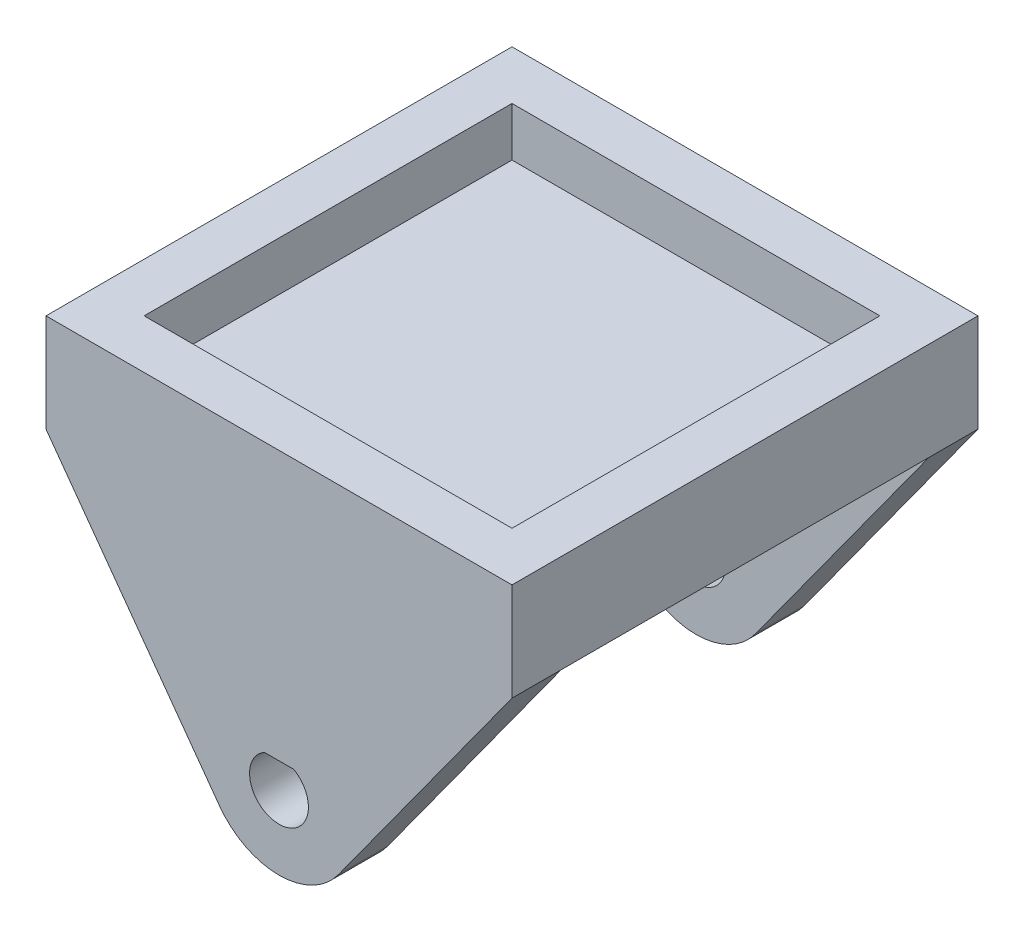
SolidWorks part; units mm, degrees
ref_plane "Front Plane" through (0, 0, 0) normal (0, 0, 1) x (1, 0, 0)
ref_plane "Top Plane" through (0, 0, 0) normal (0, 1, 0) x (1, 0, 0)
ref_plane "Right Plane" through (0, 0, 0) normal (1, 0, 0) x (0, 0, -1)
sketch "Sketch1" plane through (0, 0, 0) normal (0, 0, 1) x (1, 0, 0)
  line L0 (-3, 5.1962) -> (3, 5.1962)
  line L1 (-47.5, 40) -> (47.5, 40)
  line L2 (-12.1474, -8.8) -> (-47.5, 40)
  line L3 (12.1474, -8.8) -> (47.5, 40)
  line L4 (-47.5, 40) -> (-47.5, 60)
  line L5 (-47.5, 60) -> (47.5, 60)
  line L6 (47.5, 60) -> (47.5, 40)
  circle A0 centre (0, 0) radius 15
  circle A1 centre (0, 0) radius 6
  dimension "D1" = 30
  dimension "D2" = 12
  dimension "D3" = 6
  dimension "D4" = 40
  dimension "D5" = 95
  dimension "D7" = 20
extrude "Boss-Extrude1" add sketch "Sketch1" against normal blind 10 contours A0 L3 L1 L2 | A0 A1 | L0 A1 region at (0, 5.5196, 0) region at (0, 25.2208, 0) region at (-4.4946, 13.8655, 0)
extrude "Boss-Extrude2" add sketch "Sketch1<3>" against normal blind 95 contours L6 L5 L4 L1 region at (0, 50, 0)
sketch "Sketch1<3>" plane through (0, 0, 0) normal (0, 0, 1) x (1, 0, 0) same geometry as "Sketch1"
sketch "Sketch6" plane through (0, 40, 0) normal (0, -1, 0) x (-1, 0, 0)
  line L0 (47.5, 47.5) -> (-47.5, 47.5) construction
  line L1 (47.5, 95) -> (47.5, 10) construction
  line L2 (-47.5, 95) -> (-47.5, 10) construction
  line L3 (47.5, 95) -> (-47.5, 95) construction
  line L4 (-47.5, 47.5) -> (47.5, 47.5) construction
  dimension "D1" = 47.5
sketch "Sketch7" plane through (0, 60, 0) normal (0, 1, 0) x (1, 0, 0)
  line L0 (-47.5, 47.5) -> (47.5, 47.5) construction
  line L1 (-47.5, 95) -> (-47.5, 0) construction
ref_plane "Plane2" through (0, 0, -47.5) normal (0, 0, 1) x (1, 0, 0)
mirror "Mirror2" about plane through (0, 0, -47.5) normal (0, 0, 1) of "Boss-Extrude1"
sketch "Sketch8" plane through (0, 60, 0) normal (0, 1, 0) x (1, 0, 0)
  line L0 (-47.5, 0) -> (47.5, 0) construction
  line L1 (-37.5, 85) -> (37.5, 85)
  line L2 (-37.5, 85) -> (-37.5, 10)
  line L3 (-37.5, 10) -> (37.5, 10)
  line L4 (37.5, 85) -> (37.5, 10)
  line L5 (47.5, 95) -> (47.5, 0) construction
  line L7 (-47.5, 95) -> (-47.5, 0) construction
  line L8 (-47.5, 95) -> (47.5, 95) construction
  dimension "D1" = 10
  dimension "D2" = 10
  dimension "D3" = 10
  dimension "D4" = 10
extrude "Cut-Extrude2" cut sketch "Sketch8" against normal blind 10
